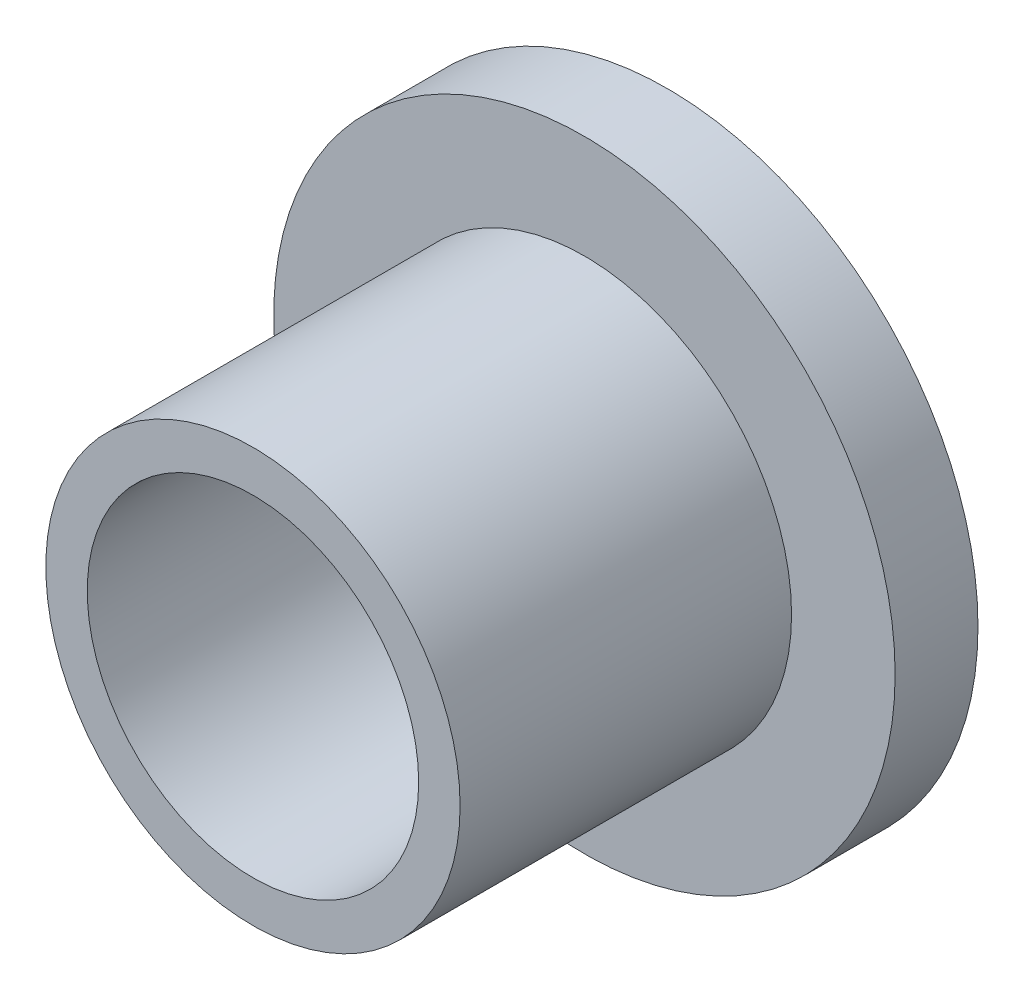
SolidWorks part; units mm, degrees
ref_plane "Front Plane" through (0, 0, 0) normal (0, 0, 1) x (1, 0, 0)
ref_plane "Top Plane" through (0, 0, 0) normal (0, 1, 0) x (1, 0, 0)
ref_plane "Right Plane" through (0, 0, 0) normal (1, 0, 0) x (0, 0, -1)
sketch "Sketch1" plane through (0, 0, 0) normal (0, 0, 1) x (1, 0, 0)
  circle A0 centre (0, 0) radius 4
  circle A1 centre (0, 0) radius 5
  circle A2 centre (0, 0) radius 7.5
  dimension "D1" = 10
  dimension "D2" = 8
  dimension "D3" = 15
extrude "Boss-Extrude1" add sketch "Sketch1" along normal blind 10 contours A1 A0 region at (-4.8586, 0, 0)
extrude "Boss-Extrude2" add sketch "Sketch1<3>" along normal blind 2 contours A2 A1 region at (-7.2879, 0, 0)
sketch "Sketch1<3>" plane through (0, 0, 0) normal (0, 0, 1) x (1, 0, 0) same geometry as "Sketch1"
